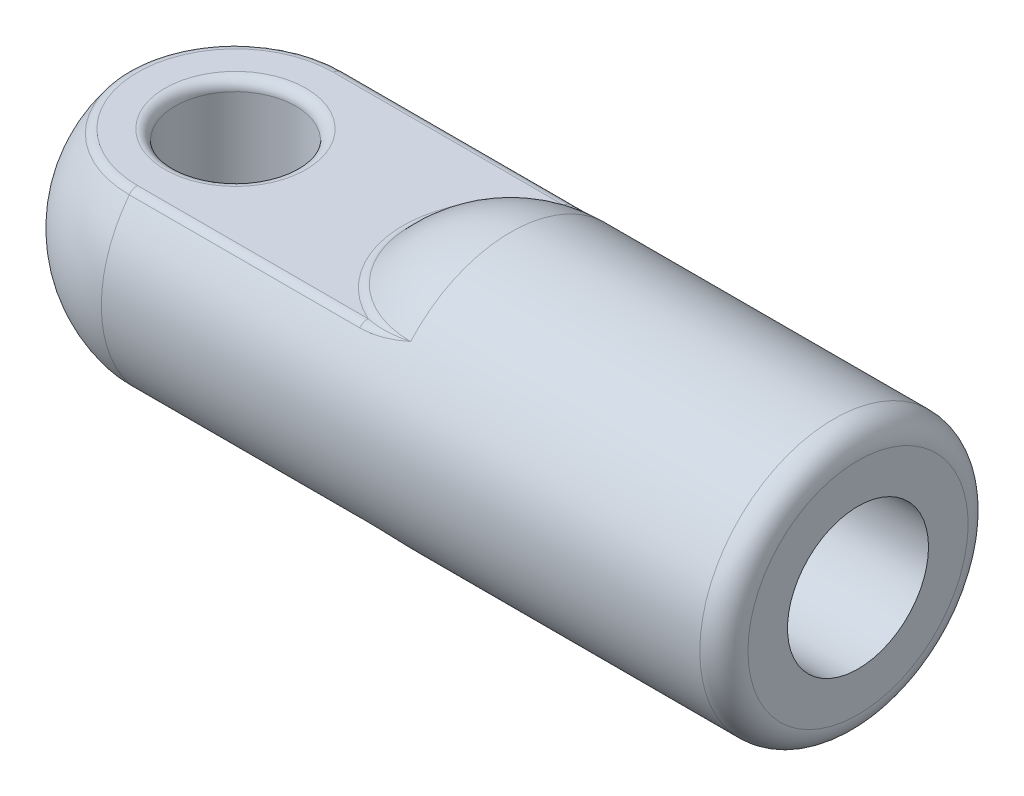
SolidWorks part; units mm, degrees
ref_plane "Front Plane" through (0, 0, 0) normal (0, 0, 1) x (1, 0, 0)
ref_plane "Top Plane" through (0, 0, 0) normal (0, 1, 0) x (1, 0, 0)
ref_plane "Right Plane" through (0, 0, 0) normal (1, 0, 0) x (0, 0, -1)
sketch "Sketch1" plane through (0, 0, 0) normal (0, 0, 1) x (1, 0, 0)
  line L0 (0, 0) -> (17.78, 0)
  line L1 (4.953, 4.953) -> (4.953, 0) construction
  line L2 (4.953, 4.953) -> (16.891, 4.953)
  line L3 (17.78, 4.064) -> (17.78, 0)
  arc A0 (0, 0) -> (4.953, 4.953) centre (4.953, 0) cw
  arc A1 (16.891, 4.953) -> (17.78, 4.064) centre (16.891, 4.064) cw
  point P4 (12.7404, -0.3252)
  dimension "D2" = 4.953
  dimension "D3" = 0.889
  dimension "D1" = 17.78
revolve "Revolve1" add sketch "Sketch1" angle 360 about L0
sketch "Sketch2" plane through (0, 0, 0) normal (0, 1, 0) x (1, 0, 0)
  line L0 (4.953, 4.953) -> (-5.207, 4.953)
  line L1 (4.953, -4.953) -> (-5.207, -4.953)
  line L2 (-5.207, 4.953) -> (-5.207, -4.953) construction
  line L3 (4.953, -4.953) -> (4.953, 4.953) construction
  line L4 (4.953, 4.953) -> (4.953, -4.953)
  arc A0 (-5.207, -4.953) -> (-5.207, 4.953) centre (-5.207, 0) cw
  dimension "D1" = 10.16
extrude "Boss-Extrude1" add sketch "Sketch2" along normal mid plane 6.35
sketch "Sketch4" plane through (4.953, 0, 0) normal (1, 0, 0) x (0, 0, -1)
  line L0 (3.8015, 3.175) -> (6.35, 3.175)
  line L1 (3.8015, -3.175) -> (6.35, -3.175)
  line L2 (6.35, 3.175) -> (6.35, -3.175)
  arc A0 (3.8015, 3.175) -> (3.8015, -3.175) centre (0, 0) cw
  dimension "D1" = 6.35
sketch "Sketch5" plane through (0, 0, 0) normal (0, 1, 0) x (1, 0, 0)
  line L0 (-5.207, -4.953) -> (4.953, -4.953) construction
  line L1 (4.953, 4.953) -> (-5.207, 4.953) construction
  line L2 (-5.207, -4.953) -> (4.953, -4.953)
  line L3 (4.953, 4.953) -> (-5.207, 4.953)
  arc A0 (-5.207, 4.953) -> (-5.207, -4.953) centre (-5.207, 0) ccw construction
  arc A1 (-5.207, 4.953) -> (-5.207, -4.953) centre (-5.207, 0) ccw
sweep "Cut-Sweep1" cut profiles "Sketch4" path "Sketch5"
sketch "Sketch6" plane through (0, 3.175, 0) normal (0, 1, 0) x (1, 0, 0)
  circle A0 centre (-5.207, 0) radius 2.2225
  arc A1 (-5.207, 3.8015) -> (-5.207, -3.8015) centre (-5.207, 0) ccw construction
  dimension "D1" = 4.445
extrude "Cut-Extrude2" cut sketch "Sketch6" against normal through all
fillet "Fillet1" radius 0.381 10 edges at (1.1515, 3.175, 0) (-0.127, 3.175, 3.8015) (-9.0085, 3.175, 0) (-0.127, 3.175, -3.8015) (-5.207, 3.175, 2.2225) (-0.127, -3.175, 3.8015) (1.1515, -3.175, 0) (-0.127, -3.175, -3.8015) (-9.0085, -3.175, 0) (-5.207, -3.175, -2.2225)
sketch "Sketch7" plane through (17.78, 0, 0) normal (1, 0, 0) x (0, 0, -1)
  circle A0 centre (0, 0) radius 2.6035
  dimension "D1" = 5.207
extrude "Cut-Extrude3" cut sketch "Sketch7" against normal blind 12.7
